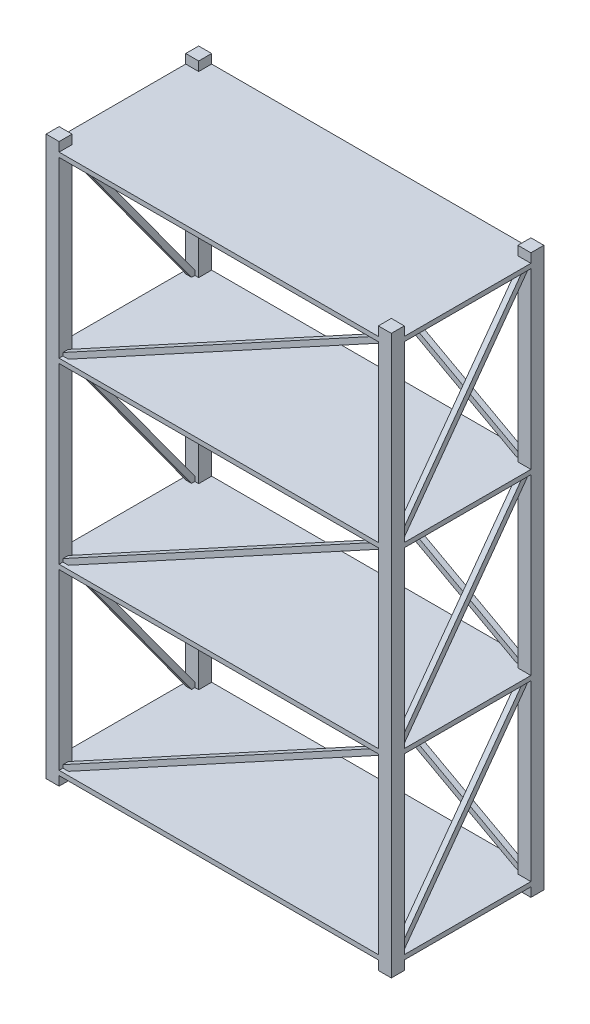
SolidWorks part; units mm, degrees
material "5052-H36"
ref_plane "Front Plane" through (0, 0, 0) normal (0, 0, 1) x (1, 0, 0)
ref_plane "Top Plane" through (0, 0, 0) normal (0, 1, 0) x (1, 0, 0)
ref_plane "Right Plane" through (0, 0, 0) normal (1, 0, 0) x (0, 0, -1)
sketch "Sketch2" plane through (0, 0, 0) normal (0, 1, 0) x (1, 0, 0)
  line L1 (-113.15, -50) -> (113.15, -50)
  line L2 (-113.15, -50) -> (-113.15, 50)
  line L3 (-113.15, 50) -> (113.15, 50)
  line L4 (113.15, -50) -> (113.15, 50)
  line L5 (-113.15, -50) -> (113.15, 50) construction
  line L6 (-113.15, 50) -> (113.15, -50) construction
  point P0 (0, 0)
  dimension "D1" = 226.3
  dimension "D2" = 100
extrude "Boss-Extrude1" add sketch "Sketch2" along normal mid plane 366
sketch "Sketch4" plane through (0, -183, 0) normal (0, -1, 0) x (1, 0, 0)
  line L5 (-113.15, 50) -> (-104.65, 50)
  line L6 (-113.15, 50) -> (-113.15, 41.5)
  line L7 (-113.15, 41.5) -> (-104.65, 41.5)
  line L8 (-104.65, 50) -> (-104.65, 41.5)
  line L9 (-113.15, -50) -> (-104.65, -50)
  line L10 (-113.15, -50) -> (-113.15, -41.5)
  line L11 (-113.15, -41.5) -> (-104.65, -41.5)
  line L16 (-104.65, -50) -> (-104.65, -41.5)
  line L17 (113.15, -50) -> (104.65, -50)
  line L18 (113.15, -50) -> (113.15, -41.5)
  line L19 (113.15, -41.5) -> (104.65, -41.5)
  line L20 (104.65, -50) -> (104.65, -41.5)
  line L21 (113.15, 50) -> (104.65, 50)
  line L22 (113.15, 50) -> (113.15, 41.5)
  line L23 (113.15, 41.5) -> (104.65, 41.5)
  line L24 (104.65, 50) -> (104.65, 41.5)
  dimension "D1" = 8.5
extrude "Cut-Extrude1" cut sketch "Sketch4" against normal blind 6 flip side to cut
mirror "Mirror1" about plane through (0, 0, 0) normal (0, 1, 0) of "Cut-Extrude1"
sketch "Sketch5" plane through (0, 0, 50) normal (0, 0, 1) x (1, 0, 0)
  line L0 (-104.65, -177) -> (-104.65, -183) construction
  line L1 (-104.65, 174) -> (104.65, 174)
  line L2 (-104.65, 174) -> (-104.65, 60)
  line L3 (-104.65, -174) -> (104.65, -174)
  line L4 (104.65, 174) -> (104.65, 60)
  line L5 (104.65, -177) -> (104.65, -183) construction
  line L6 (104.65, -177) -> (-104.65, -177) construction
  line L7 (-104.65, 177) -> (104.65, 177) construction
  line L8 (-104.65, 60) -> (104.65, 60)
  line L9 (-104.65, 57) -> (-104.65, -57)
  line L10 (104.65, 57) -> (-104.65, 57)
  line L12 (-104.65, -57) -> (104.65, -57)
  line L13 (104.65, 57) -> (104.65, -57)
  line L14 (104.65, -60) -> (-104.65, -60)
  line L15 (104.65, -60) -> (104.65, -174)
  line L16 (-104.65, -60) -> (-104.65, -174)
  line L17 (-104.65, 60) -> (-104.65, 57) construction
  line L18 (-104.65, -57) -> (-104.65, -60) construction
  line L19 (-104.65, -174) -> (-104.65, -177) construction
  dimension "D1" = 3
  dimension "D2" = 3
extrude "Cut-Extrude2" cut sketch "Sketch5" against normal through all
sketch "Sketch6" plane through (113.15, 0, 0) normal (1, 0, 0) x (0, 0, -1)
  line L8 (-41.5, 174) -> (-41.5, 60)
  line L9 (41.5, -174) -> (41.5, -60)
  line L10 (-41.5, 57) -> (-41.5, -57)
  line L11 (41.5, 60) -> (41.5, 174)
  line L12 (-50, 174) -> (-50, 60)
  line L13 (-50, 60) -> (50, 60)
  line L14 (50, 60) -> (50, 174)
  line L15 (50, 174) -> (-50, 174)
  line L17 (-41.5, 60) -> (41.5, 60)
  line L19 (41.5, 174) -> (-41.5, 174)
  line L20 (-50, 57) -> (-50, -57)
  line L21 (-50, -57) -> (50, -57)
  line L22 (50, -57) -> (50, 57)
  line L23 (50, 57) -> (-50, 57)
  line L25 (-41.5, -57) -> (41.5, -57)
  line L27 (41.5, 57) -> (-41.5, 57)
  line L28 (-50, -60) -> (-50, -174)
  line L29 (-50, -174) -> (50, -174)
  line L30 (50, -174) -> (50, -60)
  line L31 (50, -60) -> (-50, -60)
  line L33 (-41.5, -174) -> (41.5, -174)
  line L35 (41.5, -60) -> (-41.5, -60)
  line L36 (41.5, -57) -> (41.5, 57)
  line L37 (-41.5, -60) -> (-41.5, -174)
  line L38 (-41.5, -177) -> (-41.5, -183) construction
  line L39 (41.5, -177) -> (41.5, -183) construction
  dimension "D1" = 0
  dimension "D2" = 0
  dimension "D3" = 0
extrude "Cut-Extrude3" cut sketch "Sketch6" against normal through all
sketch "Sketch7" plane through (0, 0, 50) normal (0, 0, 1) x (1, 0, 0)
  line L0 (-104.65, -174) -> (104.65, -60)
  line L1 (-104.65, -57) -> (104.65, 57)
  line L2 (-104.65, 60) -> (104.65, 174)
extrude "Extrude-Thin1" add sketch "Sketch7" against normal blind 3.5 from offset 2.5 thin offset against normal yes thin type mid plane wall 3.5
sketch "Sketch8" plane through (113.15, 0, 0) normal (1, 0, 0) x (0, 0, -1)
  line L0 (-41.5, -174) -> (41.5, -60)
  line L1 (-41.5, -57) -> (41.5, 57)
  line L2 (-41.5, 60) -> (41.5, 174)
extrude "Extrude-Thin2" add sketch "Sketch8" against normal blind 3.5 from offset 2.5 thin offset against normal yes thin type mid plane wall 3.5
ref_axis "Axis1" through (0, -201.3, 0) along (0, 1, 0)
pattern_circular "CirPattern1" count 2 over 360 about axis through (0, -201.3, 0) along (0, 1, 0) of "Extrude-Thin1", "Extrude-Thin2"
